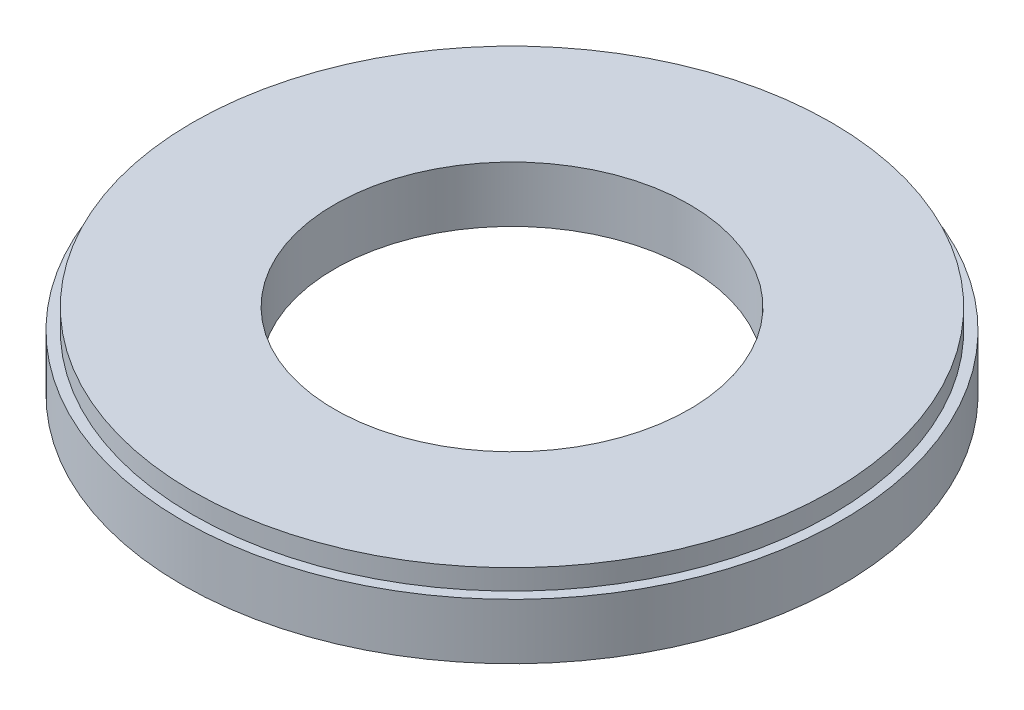
SolidWorks part; units mm, degrees
material "HYPALON"
ref_plane "Front Plane" through (0, 0, 0) normal (0, 0, 1) x (1, 0, 0)
ref_plane "Top Plane" through (0, 0, 0) normal (0, 1, 0) x (1, 0, 0)
ref_plane "Right Plane" through (0, 0, 0) normal (1, 0, 0) x (0, 0, -1)
sketch "Szkic1" plane through (0, 0, 0) normal (0, 0, 1) x (1, 0, 0)
  line L0 (0, 0) -> (-65, 0)
  line L1 (-65, 0) -> (-65, 11)
  line L2 (-65, 11) -> (-35, 11)
  line L3 (-35, 11) -> (-35, 0)
  line L4 (0, 0) -> (0, 23.5461)
  line L6 (-65, 0) -> (-63, 0)
  line L7 (-65, 0) -> (-65, -4)
  line L8 (-65, -4) -> (-63, -4)
  line L9 (-63, 0) -> (-63, -4)
  line L10 (-65, 11) -> (-63, 11)
  line L11 (-65, 11) -> (-65, 7)
  line L12 (-65, 7) -> (-63, 7)
  line L13 (-63, 11) -> (-63, 7)
  dimension "D1" = 65
  dimension "D2" = 11
  dimension "D3" = 35
  dimension "D4" = 2
  dimension "D5" = 4
  dimension "D6" = 4
  dimension "D7" = 2
revolve "Obrót1" add sketch "Szkic1" angle 360 about L4 region at (-49.6522, 5.413, 0)
